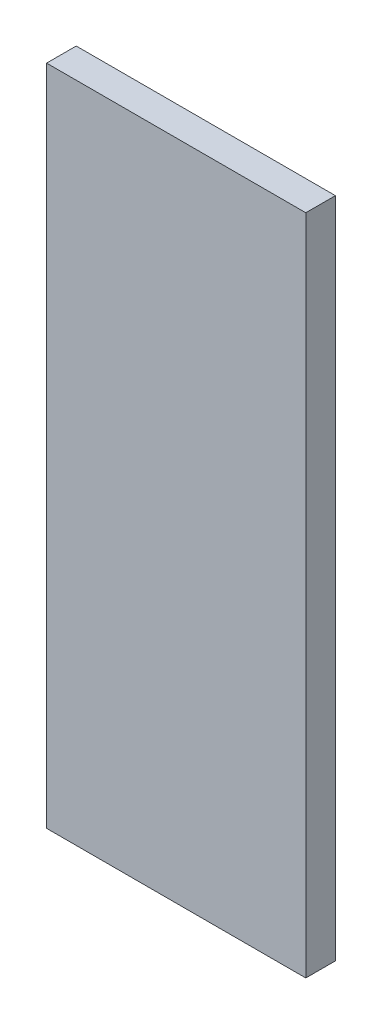
SolidWorks part; units mm, degrees
ref_plane "Front Plane" through (0, 0, 0) normal (0, 0, 1) x (1, 0, 0)
ref_plane "Top Plane" through (0, 0, 0) normal (0, 1, 0) x (1, 0, 0)
ref_plane "Right Plane" through (0, 0, 0) normal (1, 0, 0) x (0, 0, -1)
sketch "Sketch1" plane through (0, 0, 0) normal (0, 0, 1) x (1, 0, 0)
  line L1 (-16.0087, 29.2306) -> (150.6788, 29.2306)
  line L2 (-16.0087, 29.2306) -> (-16.0087, -396.9814)
  line L3 (-16.0087, -396.9814) -> (150.6788, -396.9814)
  line L4 (150.6788, 29.2306) -> (150.6788, -396.9814)
  line L5 (-16.0087, 29.2306) -> (150.6788, -396.9814) construction
  line L6 (-16.0087, -396.9814) -> (150.6788, 29.2306) construction
  point P0 (67.3351, -183.8754)
  dimension "D1" = 426.212
  dimension "D2" = 166.6875
extrude "Boss-Extrude1" add sketch "Sketch1" along normal blind 19.05 contours L2 L1 L4 L3
